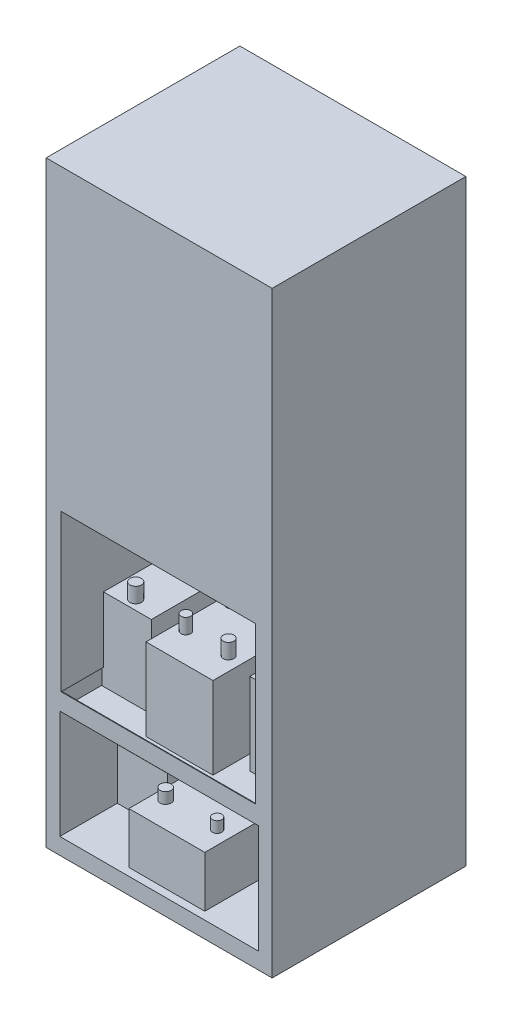
SolidWorks part; units mm, degrees
ref_plane "Alzado" through (0, 0, 0) normal (0, 0, 1) x (1, 0, 0)
ref_plane "Planta" through (0, 0, 0) normal (0, 1, 0) x (1, 0, 0)
ref_plane "Vista lateral" through (0, 0, 0) normal (1, 0, 0) x (0, 0, -1)
sketch "Croquis1" plane through (0, 0, 0) normal (0, 1, 0) x (1, 0, 0)
  line L1 (-350, 300) -> (350, 300)
  line L2 (-350, 300) -> (-350, -300)
  line L3 (-350, -300) -> (350, -300)
  line L4 (350, 300) -> (350, -300)
  line L5 (-350, 300) -> (350, -300) construction
  line L6 (-350, -300) -> (350, 300) construction
  point P0 (0, 0)
  dimension "D1" = 700
  dimension "D2" = 600
extrude "Saliente-Extruir1" add sketch "Croquis1" along normal blind 1850
sketch "Croquis2" plane through (0, 0, 300) normal (0, 0, 1) x (1, 0, 0)
  line L1 (-307.6068, 50.9) -> (307.6068, 50.9)
  line L2 (-307.6068, 50.9) -> (-307.6068, 387.2896)
  line L3 (-307.6068, 387.2896) -> (307.6068, 387.2896)
  line L4 (307.6068, 50.9) -> (307.6068, 387.2896)
  line L5 (-307.6068, 50.9) -> (307.6068, 387.2896) construction
  line L6 (-307.6068, 387.2896) -> (307.6068, 50.9) construction
  point P0 (0, 219.0948)
extrude "Cortar-Extruir1" cut sketch "Croquis2" against normal blind 1850
sketch "Croquis3" plane through (0, 0, 300) normal (0, 0, 1) x (1, 0, 0)
  line L1 (-303.7405, 925) -> (297.7312, 925)
  line L2 (-303.7405, 925) -> (-303.7405, 440.9417)
  line L3 (-303.7405, 440.9417) -> (297.7312, 440.9417)
  line L4 (297.7312, 925) -> (297.7312, 440.9417)
  line L5 (-303.7405, 925) -> (297.7312, 440.9417) construction
  line L6 (-303.7405, 440.9417) -> (297.7312, 925) construction
  point P0 (-3.0046, 682.9709)
extrude "Cortar-Extruir2" cut sketch "Croquis3" against normal blind 1850
shell "Vaciado1" thickness 2 removed face at (-3.0046, 440.9417, 0)
sketch "Croquis4" plane through (0, 389.2896, 0) normal (0, 1, 0) x (1, 0, 0)
  line L1 (149.6111, 168.6997) -> (305.4222, 168.6997)
  line L2 (149.6111, 168.6997) -> (149.6111, -168.6997)
  line L3 (149.6111, -168.6997) -> (305.4222, -168.6997)
  line L4 (305.4222, 168.6997) -> (305.4222, -168.6997)
  line L5 (149.6111, 168.6997) -> (305.4222, -168.6997) construction
  line L6 (149.6111, -168.6997) -> (305.4222, 168.6997) construction
  line L7 (-103.6465, 236.9965) -> (103.6465, 236.9965)
  line L8 (-103.6465, 236.9965) -> (-103.6465, -236.9965)
  line L9 (-103.6465, -236.9965) -> (103.6465, -236.9965)
  line L10 (103.6465, 236.9965) -> (103.6465, -236.9965)
  line L11 (-103.6465, 236.9965) -> (103.6465, -236.9965) construction
  line L12 (-103.6465, -236.9965) -> (103.6465, 236.9965) construction
  line L13 (-308.6569, 166.2136) -> (-155.4697, 166.2136)
  line L14 (-308.6569, 166.2136) -> (-308.6569, -168.6997)
  line L15 (-308.6569, -168.6997) -> (-155.4697, -168.6997)
  line L16 (-155.4697, 166.2136) -> (-155.4697, -168.6997)
  line L17 (-308.6569, 166.2136) -> (-155.4697, -168.6997) construction
  line L18 (-308.6569, -168.6997) -> (-155.4697, 166.2136) construction
  point P0 (227.5167, 0)
  point P5 (0, 0)
  point P11 (-232.0633, -1.2431)
extrude "Saliente-Extruir2" add sketch "Croquis4" along normal blind 254
sketch "Croquis5" plane through (0, 643.2896, 0) normal (0, 1, 0) x (1, 0, 0)
  circle A0 centre (230.0446, -120.7102) radius 17.6957
  circle A1 centre (230.0446, 47.3993) radius 17.6957
  circle A2 centre (-71.1508, -146.027) radius 14.8785
  circle A3 centre (-71.1508, 0) radius 20.0461
  circle A4 centre (-234.15, -138.406) radius 17.6957
  circle A5 centre (-234.15, 47.3993) radius 15.6127
  circle A6 centre (-71.1508, 166.6036) radius 20.0697
  circle A7 centre (61.0037, 0) radius 21.5153
  circle A8 centre (61.0037, 166.6036) radius 19.1168
  circle A9 centre (61.0037, -146.027) radius 16.4298
extrude "Saliente-Extruir3" add sketch "Croquis5" along normal blind 47
sketch "Croquis6" plane through (0, 50.9, 0) normal (0, 1, 0) x (1, 0, 0)
  line L1 (117.5503, -276.1799) -> (-117.5503, -276.1799)
  line L2 (117.5503, -276.1799) -> (117.5503, 276.1799)
  line L3 (117.5503, 276.1799) -> (-117.5503, 276.1799)
  line L4 (-117.5503, -276.1799) -> (-117.5503, 276.1799)
  line L5 (117.5503, -276.1799) -> (-117.5503, 276.1799) construction
  line L6 (117.5503, 276.1799) -> (-117.5503, -276.1799) construction
  line L7 (-152.4825, -121.9742) -> (-307.6068, -121.9742)
  line L8 (-152.4825, -121.9742) -> (-152.4825, 121.9742)
  line L9 (-152.4825, 121.9742) -> (-307.6068, 121.9742)
  line L10 (-307.6068, -121.9742) -> (-307.6068, 121.9742)
  line L11 (-152.4825, -121.9742) -> (-307.6068, 121.9742) construction
  line L12 (-152.4825, 121.9742) -> (-307.6068, -121.9742) construction
  line L13 (289.4517, -121.9742) -> (152.9417, -121.9742)
  line L14 (289.4517, -121.9742) -> (289.4517, 121.9742)
  line L15 (289.4517, 121.9742) -> (152.9417, 121.9742)
  line L16 (152.9417, -121.9742) -> (152.9417, 121.9742)
  line L17 (289.4517, -121.9742) -> (152.9417, 121.9742) construction
  line L18 (289.4517, 121.9742) -> (152.9417, -121.9742) construction
  point P0 (0, 0)
  point P6 (-230.0446, 0)
  point P11 (221.1967, 0)
extrude "Saliente-Extruir4" add sketch "Croquis6" along normal blind 158
sketch "Croquis7" plane through (0, 208.9, 0) normal (0, 1, 0) x (1, 0, 0)
  circle A0 centre (220.4901, -83.4417) radius 21.3099
  circle A1 centre (220.4901, 65.5487) radius 19.7092
  circle A2 centre (-83.7177, -196.0122) radius 17.1385
  circle A3 centre (75.6701, -196.0122) radius 14.5387
  circle A4 centre (-83.7177, 0) radius 19.1962
  circle A5 centre (75.6701, 5.9526) radius 15.4246
  circle A6 centre (-83.7177, 184.741) radius 17.9954
  circle A7 centre (75.6701, 184.741) radius 20.52
  circle A8 centre (-230.0446, -62.1317) radius 17.445
  circle A9 centre (-230.0446, 45.8395) radius 21.1159
extrude "Saliente-Extruir5" add sketch "Croquis7" along normal blind 34
sketch "Croquis8" plane through (0, 0, -300) normal (0, 0, -1) x (-1, 0, 0)
  line L1 (-250.0903, 1244.3934) -> (250.0903, 1244.3934)
  line L2 (-300.0903, 1294.3934) -> (-300.0903, 1716.6284)
  line L3 (-250.0903, 1766.6284) -> (250.0903, 1766.6284)
  line L4 (300.0903, 1294.3934) -> (300.0903, 1716.6284)
  line L5 (-300.0903, 1244.3934) -> (300.0903, 1766.6284) construction
  line L6 (-300.0903, 1766.6284) -> (300.0903, 1244.3934) construction
  arc A0 (-250.0903, 1244.3934) -> (-300.0903, 1294.3934) centre (-250.0903, 1294.3934) cw
  arc A1 (250.0903, 1244.3934) -> (300.0903, 1294.3934) centre (250.0903, 1294.3934) ccw
  arc A2 (250.0903, 1766.6284) -> (300.0903, 1716.6284) centre (250.0903, 1716.6284) cw
  arc A3 (-300.0903, 1716.6284) -> (-250.0903, 1766.6284) centre (-250.0903, 1716.6284) cw
  point P0 (0, 1505.5109)
  dimension "D1" = 50
extrude "Saliente-Extruir6" add sketch "Croquis8" along normal blind 34
sketch "Croquis9" plane through (0, 0, -334) normal (0, 0, -1) x (-1, 0, 0)
  line L1 (-278.6006, 1733.8635) -> (-181.3334, 1733.8635)
  line L2 (-278.6006, 1733.8635) -> (-278.6006, 1654.2812)
  line L3 (-278.6006, 1654.2812) -> (-181.3334, 1654.2812)
  line L4 (-181.3334, 1733.8635) -> (-181.3334, 1654.2812)
  line L5 (-278.6006, 1733.8635) -> (-181.3334, 1654.2812) construction
  line L6 (-278.6006, 1654.2812) -> (-181.3334, 1733.8635) construction
  line L7 (-2.0629, 1491.6936) -> (254.3691, 1491.6936)
  line L8 (-2.0629, 1491.6936) -> (-2.0629, 1336.9502)
  line L9 (-2.0629, 1336.9502) -> (254.3691, 1336.9502)
  line L10 (254.3691, 1491.6936) -> (254.3691, 1336.9502)
  line L11 (-2.0629, 1491.6936) -> (254.3691, 1336.9502) construction
  line L12 (-2.0629, 1336.9502) -> (254.3691, 1491.6936) construction
  point P0 (-229.967, 1694.0724)
  point P5 (126.1531, 1414.3219)
extrude "Cortar-Extruir3" cut sketch "Croquis9" against normal blind 0.2
sketch "Croquis10" plane through (0, 0, -334) normal (0, 0, -1) x (-1, 0, 0)
  line L0 (-266.9064, 1336.5019) -> (-114.6168, 1336.5019) construction
  text T0 "MEJ" font "Century Gothic" height in points 250
extrude "Cortar-Extruir4" cut sketch "Croquis10" against normal blind 0.2
sketch "Croquis11" plane through (0, 0, -300) normal (0, 0, -1) x (-1, 0, 0)
  circle A0 centre (-331.1303, 1826.0494) radius 8.6382
  circle A1 centre (331.4196, 1826.0494) radius 9.502
extrude "Cortar-Extruir5" cut sketch "Croquis11" against normal blind 0.2
pattern_linear "MatrizL1" count 36 spacing 50 along (0, -1, 0) of "Cortar-Extruir5"
sketch "Croquis12" plane through (0, 0, -300) normal (0, 0, -1) x (-1, 0, 0)
  circle A0 centre (-277.5665, 414.7202) radius 7.9
extrude "Cortar-Extruir6" cut sketch "Croquis12" against normal blind 0.2
pattern_linear "MatrizL2" count 30 spacing 20 along (-1, 0, 0) of "Cortar-Extruir6"
